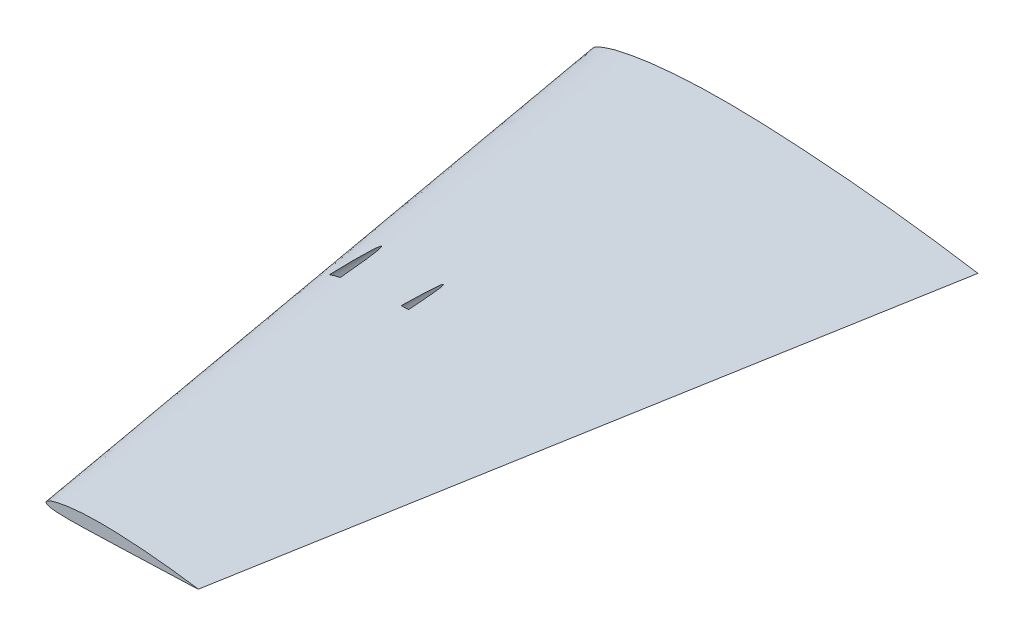
SolidWorks part; units mm, degrees
ref_plane "Front Plane" through (0, 0, 0) normal (0, 0, 1) x (1, 0, 0)
ref_plane "Top Plane" through (0, 0, 0) normal (0, 1, 0) x (1, 0, 0)
ref_plane "Right Plane" through (0, 0, 0) normal (1, 0, 0) x (0, 0, -1)
sketch "Sketch8" plane through (0, 0, 0) normal (0, 0, 1) x (1, 0, 0)
  line L0 (168.8513, -0.3858) -> (177.8, 0.1494)
  spline S1 degree 3 poles (177.8, 0.1494) (174.8572, 0.6127) (168.9691, 1.5397) (157.169, 3.2406) (142.3871, 5.1395) (124.6124, 7.0685) (106.8068, 8.6377) (88.9752, 9.7996) (71.092, 10.5503) (56.1512, 10.6038) (44.1821, 10.1401) (35.2131, 9.5128) (26.2593, 8.5598) (18.8302, 7.419) (12.914, 6.1924) (8.4874, 5.1255) (4.7939, 3.7) (1.8287, 2.5653) (-1.1793, -0.1236) (2.2999, -2.1293) (5.3722, -2.8156) (9.2491, -3.4189) (13.7179, -3.775) (19.6653, -4.0651) (27.0506, -4.1896) (35.8934, -4.1425) (44.7107, -3.9908) (56.4508, -3.7102) (71.1567, -3.3279) (88.8377, -2.8334) (106.5685, -2.2446) (124.325, -1.67) (142.1131, -1.1221) (156.9587, -0.7066) (165.8755, -0.4661) (168.8513, -0.3858) knots 0 0 0 0 0.025516 0.051054 0.102112 0.153157 0.204181 0.255198 0.306199 0.357469 0.383114 0.408778 0.434465 0.460211 0.473144 0.486144 0.499401 0.506173 0.51522 0.524256 0.531058 0.544124 0.55697 0.569703 0.595038 0.620263 0.645429 0.670573 0.720845 0.771431 0.822073 0.872796 0.923598 0.974503 1 1 1 1
  dimension "D1" = 177.8
ref_plane "Plane2" through (0, 0, 304.8) normal (0, 0, 1) x (1, 0, 0)
sketch "Sketch9" plane through (0, 0, 304.8) normal (0, 0, 1) x (1, 0, 0)
  line L0 (120.4249, -0.4411) -> (123.952, -0.2104)
  line L1 (-53.8736, -0.2104) -> (123.952, -0.2104) construction
  line L2 (53.848, -28.5193) -> (53.848, 0.0003) construction
  spline S1 degree 3 poles (123.952, -0.2104) (122.7907, -0.0342) (120.4671, 0.3184) (115.8109, 0.9631) (109.9786, 1.6794) (102.9662, 2.4009) (95.9425, 2.9805) (88.9093, 3.3995) (81.8568, 3.6562) (75.9659, 3.6445) (71.2478, 3.4354) (67.7129, 3.1684) (64.1847, 2.773) (61.2581, 2.3069) (58.9282, 1.8103) (57.1852, 1.38) (55.7321, 0.8098) (54.5655, 0.3559) (53.3854, -0.7108) (54.7616, -1.494) (55.9744, -1.7579) (57.5043, -1.9872) (59.267, -2.1178) (61.6126, -2.2191) (64.5247, -2.252) (68.0111, -2.214) (71.4872, -2.1349) (76.1154, -1.9985) (81.9128, -1.8155) (88.8829, -1.5817) (95.8724, -1.3106) (102.8721, -1.0451) (109.8843, -0.7901) (115.7366, -0.5937) (119.2518, -0.4793) (120.4249, -0.4411) knots 0 0 0 0 0.025516 0.051054 0.102112 0.153157 0.204181 0.255198 0.306199 0.357469 0.383114 0.408778 0.434465 0.460211 0.473144 0.486144 0.499401 0.506173 0.51522 0.524256 0.531058 0.544124 0.55697 0.569703 0.595038 0.620263 0.645429 0.670573 0.720845 0.771431 0.822073 0.872796 0.923598 0.974503 1 1 1 1
  dimension "D1" = 70.104
  dimension "D2" = 53.848
loft "Loft1" add profiles "Sketch8", "Sketch9"
sketch "Sketch10" plane through (0, 0, 0) normal (0, 0, -1) x (-1, 0, 0)
  line L0 (-66.6146, 3.9236) -> (-34.9854, 1.1564) construction
  line L1 (0, 0) -> (-67.4489, 0) construction
  circle A0 centre (-66.6146, 3.9236) radius 3.556
  circle A1 centre (-34.9854, 1.1564) radius 3.556
  point P5 (-50.8, 2.54)
  point P8 (0, 0)
  point P11 (-43.3328, 0)
  dimension "D3" = 7.112
  dimension "D1" = 5
  dimension "D2" = 31.75
  dimension "D4" = 50.8
  dimension "D5" = 2.54
extrude "Cut-Extrude1" cut sketch "Sketch10" against normal blind 152.4
